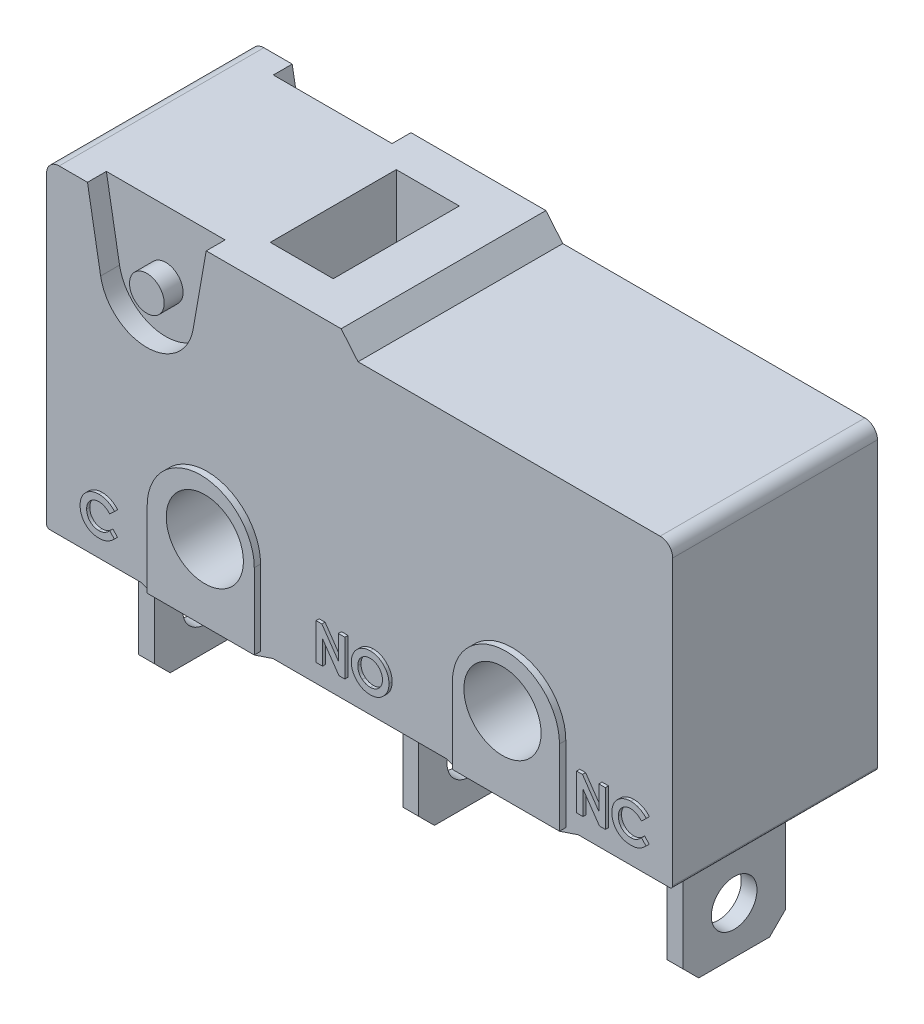
SolidWorks part; units mm, degrees
ref_plane "Front Plane" through (0, 0, 0) normal (0, 0, 1) x (1, 0, 0)
ref_plane "Top Plane" through (0, 0, 0) normal (0, 1, 0) x (1, 0, 0)
ref_plane "Right Plane" through (0, 0, 0) normal (1, 0, 0) x (0, 0, -1)
sketch "Sketch1" plane through (0, 0, 0) normal (0, 0, 1) x (1, 0, 0)
  line L0 (9.353, 0) -> (9.89, -0.64)
  line L1 (0.4, 0) -> (9.353, 0)
  line L2 (0, -0.4) -> (0, -10.15)
  line L3 (0, -10.15) -> (3, -10.15)
  line L4 (19.88, -1.04) -> (19.88, -10.15)
  line L5 (9.89, -0.64) -> (19.48, -0.64)
  line L6 (3, -10.15) -> (3.595, -10.35)
  line L7 (3.595, -10.35) -> (6.595, -10.35)
  line L8 (6.595, -10.35) -> (7.19, -10.15)
  line L9 (12.69, -10.15) -> (13.285, -10.35)
  line L10 (13.285, -10.35) -> (16.285, -10.35)
  line L11 (16.285, -10.35) -> (16.88, -10.15)
  line L12 (7.19, -10.15) -> (12.69, -10.15)
  line L13 (16.88, -10.15) -> (19.88, -10.15)
  arc A0 (0.4, 0) -> (0, -0.4) centre (0.4, -0.4) ccw
  arc A1 (19.48, -0.64) -> (19.88, -1.04) centre (19.48, -1.04) cw
  point P10 (0, 0)
  dimension "D1" = 0.4
  dimension "D2" = 10.15
  dimension "D3" = 9.51
  dimension "D4" = 9.89
  dimension "D5" = 130
  dimension "D6" = 19.88
  dimension "D7" = 3
  dimension "D8" = 3
  dimension "D9" = 3
  dimension "D10" = 5.5
  dimension "D11" = 0.2
extrude "Boss-Extrude1" add sketch "Sketch1" along normal blind 6.5
sketch "Sketch3" plane through (0, 0, 6.5) normal (0, 0, 1) x (1, 0, 0)
  line L0 (3.395, -7.75) -> (3.395, -10.15)
  line L1 (3.395, -10.15) -> (6.795, -10.15)
  line L2 (6.795, -10.15) -> (6.795, -7.75)
  line L3 (3.595, -10.35) -> (6.595, -10.35) construction
  line L4 (5.095, -6.05) -> (14.785, -6.05) construction
  line L5 (7.19, -10.15) -> (12.69, -10.15) construction
  line L6 (13.085, -7.75) -> (13.085, -10.15)
  line L7 (13.085, -10.15) -> (16.485, -10.15)
  line L8 (16.485, -10.15) -> (16.485, -7.75)
  line L9 (13.285, -10.35) -> (16.285, -10.35) construction
  arc A0 (3.395, -7.75) -> (6.795, -7.75) centre (5.095, -7.75) cw
  arc A1 (13.085, -7.75) -> (16.485, -7.75) centre (14.785, -7.75) cw
  point P5 (5.095, -10.15)
  point P6 (5.095, -10.35)
  point P18 (14.785, -10.35)
  point P19 (14.785, -10.15)
  dimension "D1" = 3.4
  dimension "D2" = 4.1
extrude "Boss-Extrude2" add sketch "Sketch3" along normal blind 0.2
ref_plane "Plane1" through (0, 0, 3.25) normal (0, 0, 1) x (1, 0, 0)
mirror "Mirror1" about plane through (0, 0, 3.25) normal (0, 0, 1) of "Boss-Extrude2"
sketch "Sketch4" plane through (0, 0, 6.7) normal (0, 0, 1) x (1, 0, 0)
  circle A0 centre (5.2252, -7.7506) radius 1.225
  circle A1 centre (14.6752, -7.75) radius 1.225
  dimension "D1" = 2.45
  dimension "D2" = 9.45
extrude "Cut-Extrude1" cut sketch "Sketch4" against normal blind 10.2
fillet "Fillet1" radius 0.1 2 edges at (19.88, -10.15, 3.25) (0, -10.15, 3.25)
sketch "Sketch5" plane through (0, 0, 6.5) normal (0, 0, 1) x (1, 0, 0)
  line L0 (1.7177, -2.3688) -> (1.3, 0)
  line L1 (9.353, 0) -> (0.4, 0) construction
  line L2 (4.6523, -2.3688) -> (5.07, 0)
  line L3 (3.185, -3.6) -> (0, -3.6) construction
  line L4 (0, -0.4) -> (0, -10.05) construction
  line L5 (1.3, 0) -> (5.07, 0)
  arc A0 (1.7177, -2.3688) -> (4.6523, -2.3688) centre (3.185, -2.11) ccw
  circle A1 centre (3.185, -2.11) radius 0.55
  dimension "D5" = 1.1
  dimension "D1" = 3.6
  dimension "D2" = 1.3
  dimension "D3" = 3.77
  dimension "D4" = 100
extrude "Cut-Extrude2" cut sketch "Sketch5" against normal blind 0.6
mirror "Mirror2" about plane through (0, 0, 3.25) normal (0, 0, 1) of "Cut-Extrude2"
sketch "Sketch6" plane through (0, 0, 0) normal (0, 1, 0) x (1, 0, 0)
  line L0 (9.353, -6.5) -> (9.353, 0) construction
  line L1 (5.853, -1.25) -> (7.853, -1.25)
  line L2 (5.853, -1.25) -> (5.853, -5.25)
  line L3 (5.853, -5.25) -> (7.853, -5.25)
  line L4 (7.853, -1.25) -> (7.853, -5.25)
  point P4 (9.353, -3.25)
  point P5 (7.853, -3.25)
  dimension "D1" = 2
  dimension "D2" = 4
  dimension "D3" = 1.5
extrude "Cut-Extrude3" cut sketch "Sketch6" against normal blind 2
sketch "Sketch7" plane through (0, -10.15, 0) normal (0, -1, 0) x (1, 0, 0)
  line L0 (0.1, 6.5) -> (3, 6.5) construction
  line L1 (1.3, 4.875) -> (1.8, 4.875)
  line L2 (1.3, 4.875) -> (1.3, 1.625)
  line L3 (1.3, 1.625) -> (1.8, 1.625)
  line L4 (1.8, 4.875) -> (1.8, 1.625)
  line L5 (9.69, 4.875) -> (10.19, 4.875)
  line L6 (9.69, 4.875) -> (9.69, 1.625)
  line L7 (9.69, 1.625) -> (10.19, 1.625)
  line L8 (10.19, 4.875) -> (10.19, 1.625)
  line L9 (18.08, 4.875) -> (18.58, 4.875)
  line L10 (18.08, 4.875) -> (18.08, 1.625)
  line L11 (18.08, 1.625) -> (18.58, 1.625)
  line L12 (18.58, 4.875) -> (18.58, 1.625)
  line L13 (7.19, 6.5) -> (12.69, 6.5) construction
  line L14 (16.88, 6.5) -> (19.78, 6.5) construction
  line L15 (3, 6.5) -> (3, 0) construction
  point P12 (1.55, 6.5)
  point P13 (1.55, 4.875)
  point P16 (9.94, 4.875)
  point P17 (9.94, 6.5)
  point P18 (18.33, 4.875)
  point P21 (18.33, 6.5)
  point P22 (3, 3.25)
  point P25 (1.8, 3.25)
  point P28 (9.69, 3.25)
  point P29 (18.08, 3.25)
  dimension "D1" = 3.25
  dimension "D2" = 0.5
extrude "Boss-Extrude3" add sketch "Sketch7" along normal blind 4.15
chamfer "Chamfer1" distance 0.5 angle 45 6 edges at (1.55, -14.3, 4.875) (9.94, -14.3, 4.875) (18.33, -14.3, 4.875) (18.33, -14.3, 1.625) (9.94, -14.3, 1.625) (1.55, -14.3, 1.625)
sketch "Sketch8" plane through (1.3, 0, 0) normal (-1, 0, 0) x (0, 0, 1)
  line L0 (4.375, -14.3) -> (2.125, -14.3) construction
  circle A0 centre (3.25, -12.8) radius 0.725
  point P2 (3.25, -14.3)
  dimension "D1" = 1.45
  dimension "D2" = 1.5
extrude "Cut-Extrude4" cut sketch "Sketch8" against normal blind 18.15
sketch "Sketch9" plane through (0, 0, 6.5) normal (0, 0, 1) x (1, 0, 0)
  text T0 "C              NO             NC" font "Century Gothic" height 1.15
extrude "Boss-Extrude4" add sketch "Sketch9" along normal blind 0.1
sketch "Sketch11" plane through (0, 0, 0) normal (0, 0, -1) x (-1, 0, 0)
  text T0 "KW       CE" font "Century Gothic" height 1.78
extrude "Boss-Extrude5" add sketch "Sketch11" along normal blind 0.1
sketch "Sketch12" plane through (0, 0, 0) normal (0, 0, -1) x (-1, 0, 0)
  text T0 "5A  125  250V" font "Century Gothic" height 1.3
extrude "Boss-Extrude6" add sketch "Sketch12" along normal blind 0.1
sketch "Sketch13" plane through (0, 0, 0) normal (0, 0, -1) x (-1, 0, 0)
  text T0 "2                  3                  1" font "Century Gothic" height 1.1
extrude "Boss-Extrude7" add sketch "Sketch13" along normal blind 0.1
sketch "Sketch14" plane through (0, 0, 0) normal (0, 0, -1) x (-1, 0, 0)
  line L0 (-18.2761, -7.6793) -> (-18.2761, -5.3079)
  line L1 (-18.2761, -5.3079) -> (-9.8134, -5.3079)
  line L2 (-9.8134, -5.3079) -> (-9.8134, -5.5774)
  line L3 (-9.8134, -7.7817) -> (-9.8134, -6.3917)
  line L4 (-3.5611, -6.0907) -> (-1.3125, -6.0907)
  line L5 (-1.3125, -6.0907) -> (-1.3125, -7.532)
  line L6 (-1.3125, -7.532) -> (-1.3625, -7.532)
  line L7 (-1.3625, -7.532) -> (-1.3625, -6.1407)
  line L8 (-1.3625, -6.1407) -> (-3.5611, -6.1407)
  line L9 (-3.5611, -6.1407) -> (-3.5611, -6.0907)
  line L10 (-18.2761, -7.6793) -> (-18.2261, -7.6793)
  line L11 (-18.2261, -7.6793) -> (-18.2261, -5.3579)
  line L12 (-18.2261, -5.3579) -> (-9.8634, -5.3579)
  line L13 (-9.8634, -5.3579) -> (-9.8634, -5.5774)
  line L14 (-9.8634, -5.5774) -> (-10.0384, -5.5774)
  line L15 (-10.0384, -5.5774) -> (-9.8384, -5.7774)
  line L16 (-9.8384, -5.7774) -> (-9.6384, -5.5774)
  line L17 (-9.6384, -5.5774) -> (-9.8134, -5.5774)
  line L18 (-9.8134, -7.7817) -> (-9.8634, -7.7817)
  line L19 (-9.8634, -7.7817) -> (-9.8634, -6.3917)
  line L20 (-9.8634, -6.3917) -> (-10.0384, -6.3917)
  line L21 (-10.0384, -6.3917) -> (-9.8384, -6.1917)
  line L22 (-9.8384, -6.1917) -> (-9.6384, -6.3917)
  line L23 (-9.6384, -6.3917) -> (-9.8134, -6.3917)
  line L24 (-9.8634, -5.3079) -> (-9.8634, -5.3579) construction
  line L25 (-9.8634, -5.3579) -> (-9.8134, -5.3579) construction
  line L26 (-9.8384, -6.0124) -> (-8.7652, -6.1417)
  line L27 (-8.7652, -6.1417) -> (-7.7787, -6.1417)
  line L28 (-7.7787, -6.1417) -> (-7.7787, -6.1917)
  line L29 (-7.7787, -6.1917) -> (-8.7652, -6.1917)
  line L30 (-8.7652, -6.1917) -> (-9.8384, -6.0624)
  line L31 (-9.8384, -6.0624) -> (-9.8384, -6.0124)
  line L32 (-9.8634, -5.5774) -> (-9.8134, -5.5774) construction
  point P28 (-9.8384, -5.5774)
  dimension "D1" = 0.05
  dimension "D2" = 0.05
  dimension "D3" = 0.2
  dimension "D4" = 0.2
extrude "Boss-Extrude8" add sketch "Sketch14" along normal blind 0.1
sketch "Sketch15" plane through (0, 0, 0) normal (0, 0, -1) x (-1, 0, 0)
  line L0 (-5.9919, -3.9223) -> (-5.0693, -3.2965) construction
  line L1 (-5.0693, -3.2965) -> (-5.0693, -4.5481) construction
  line L2 (-5.0693, -4.5481) -> (-4.1468, -3.9223) construction
  line L4 (-5.9919, -4.0227) -> (-5.0693, -3.3969) construction
  line L5 (-5.0693, -3.3969) -> (-5.0693, -4.6486) construction
  line L6 (-5.0693, -4.6486) -> (-4.1468, -4.0227) construction
  line L7 (-4.1468, -3.9223) -> (-4.1468, -4.0227)
  line L8 (-5.9919, -3.9223) -> (-5.9919, -4.0227)
  spline S0 degree 3 poles (-5.9919, -3.9223) (-5.0693, -3.2965) (-5.0693, -4.5481) (-4.1468, -3.9223) knots 0 0 0 0 1 1 1 1
  spline S1 degree 3 poles (-5.9919, -4.0227) (-5.0693, -3.3969) (-5.0693, -4.6486) (-4.1468, -4.0227) knots 0 0 0 0 1 1 1 1
  dimension "D1" = 0.1004
extrude "Boss-Extrude9" add sketch "Sketch15" along normal blind 0.1
ref_plane "Plane2" through (0, 0, 3.25) normal (0, 0, -1) x (-1, 0, 0)
sketch "Sketch17" plane through (18.58, 0, 0) normal (1, 0, 0) x (0, 0, -1)
  circle A0 centre (-3.25, -12.8) radius 0.725
extrude "Boss-Extrude11" [suppressed] add sketch "Sketch17" against normal blind 3 and the other way blind 1
sketch "Sketch18" [suppressed] plane through (1.8, 0, 0) normal (1, 0, 0) x (0, 0, -1)
  circle A0 centre (-3.25, -12.8) radius 0.725
extrude "Boss-Extrude12" [suppressed] add sketch "Sketch18" against normal blind 3 and the other way blind 1
